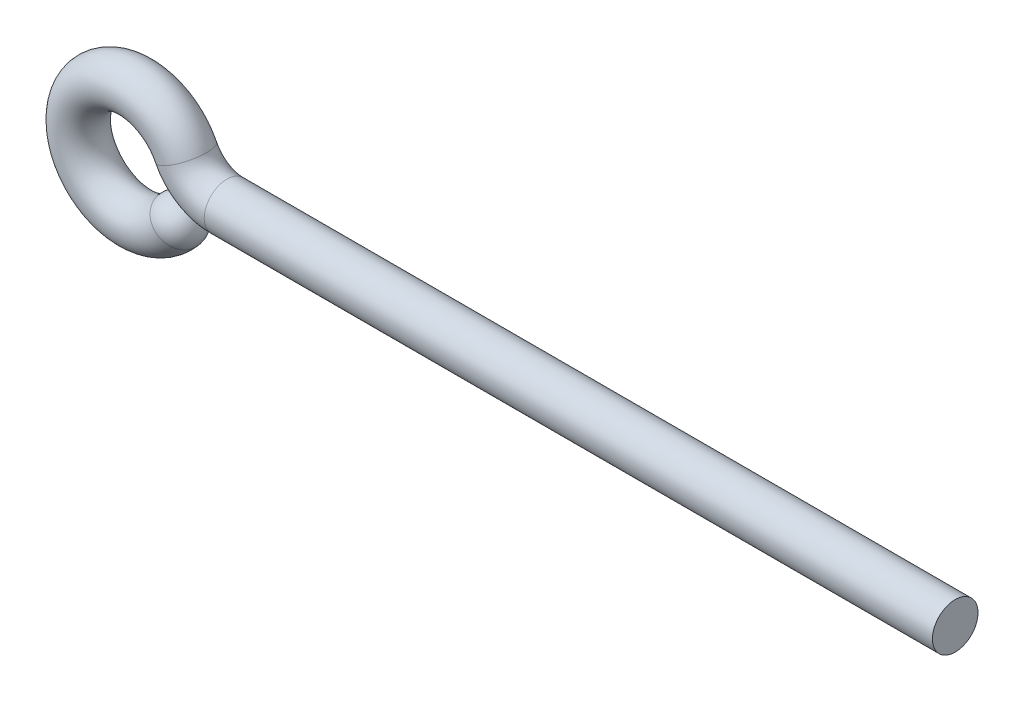
SolidWorks part; units mm, degrees
ref_plane "Front Plane" through (0, 0, 0) normal (0, 0, 1) x (1, 0, 0)
ref_plane "Top Plane" through (0, 0, 0) normal (0, 1, 0) x (1, 0, 0)
ref_plane "Right Plane" through (0, 0, 0) normal (1, 0, 0) x (0, 0, -1)
sketch "Sketch1" plane through (0, 0, 0) normal (0, 0, 1) x (1, 0, 0)
  line L0 (0, 0) -> (-6, 0) construction
  line L1 (-6, 0) -> (-4.0849, -1.607) construction
  line L2 (-1.9689, 0) -> (0, 0)
  arc A0 (-3.7605, 1.1111) -> (-4.0849, -1.607) centre (-6, 0) ccw
  arc A1 (-3.7605, 1.1111) -> (-1.9689, 0) centre (-1.9689, 2) ccw
  point P7 (-3.5, 0)
  dimension "D2" = 2.5
  dimension "D4" = 2
  dimension "D1" = 6
  dimension "D3" = 40
sketch "Sketch2" plane through (0, 0, 0) normal (1, 0, 0) x (0, 0, -1)
  line L0 (0, 2.5) -> (0, -2.5) construction
  circle A0 centre (0, 0) radius 1
  dimension "D1" = 2
sweep "Sweep1" add profiles "Sketch2" path "Sketch1"
sketch "Sketch3" plane through (0, 0, 0) normal (1, 0, 0) x (0, 0, -1)
  circle A1 centre (0, 0) radius 1
  circle A2 centre (0, 0) radius 1
  dimension "D1" = 0
extrude "Boss-Extrude1" add sketch "Sketch3" along normal blind 30
dome "Dome1" faces to dome 1 distance 1 reverse direction no elliptical dome no face at (-4.0849, -1.607, -1) parameters "D1"=1
sketch "Sketch4" plane through (0, 0, 0) normal (0, 0, 1) x (1, 0, 0)
  circle A0 centre (-6, 0) radius 1.5
